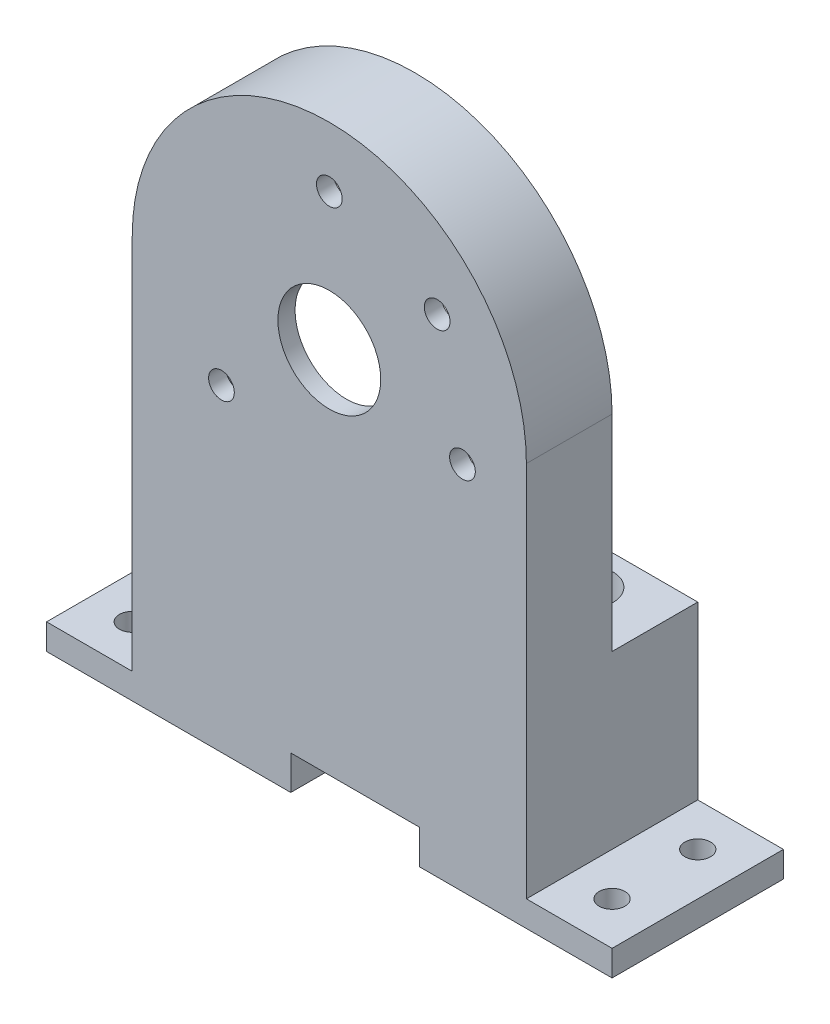
SolidWorks part; units mm, degrees
ref_plane "前视基准面" through (0, 0, 0) normal (0, 0, 1) x (1, 0, 0)
ref_plane "上视基准面" through (0, 0, 0) normal (0, 1, 0) x (1, 0, 0)
ref_plane "右视基准面" through (0, 0, 0) normal (1, 0, 0) x (0, 0, -1)
other "Configuration Table"
sketch "草图1" plane through (0, 0, 0) normal (0, 0, 1) x (1, 0, 0)
  line L0 (-23, 0) -> (-23, -27)
  line L1 (-23, -27) -> (23, -27)
  line L2 (23, -27) -> (23, 0)
  arc A1 (23, 0) -> (-23, 0) centre (0, 0) ccw
  dimension "D1" = 27
  dimension "D2" = 23
extrude "凸台-拉伸1" add sketch "草图1" along normal blind 20
sketch "草图2" plane through (0, 0, 0) normal (0, 0, -1) x (-1, 0, 0)
  line L0 (-23, -24) -> (23, -24)
  line L1 (23, 0) -> (23, -27) construction
  line L2 (-23, -27) -> (-23, 0) construction
  line L3 (-23, 0) -> (-23, -27)
  line L4 (-23, -27) -> (23, -27)
  line L5 (23, -27) -> (23, 0)
  line L6 (-23, 0) -> (-23, -24)
  line L8 (23, -24) -> (23, 0)
  arc A1 (23, 0) -> (-23, 0) centre (0, 0) ccw
  arc A2 (23, 0) -> (-23, 0) centre (0, 0) ccw
  dimension "D2" = 24
  dimension "D1" = 0
extrude "切除-拉伸1" cut sketch "草图2" against normal blind 10
sketch "草图3" plane through (0, 0, 10) normal (0, 0, -1) x (-1, 0, 0)
  circle A0 centre (0, 0) radius 21
extrude "切除-拉伸2" cut sketch "草图3" against normal blind 8
sketch "草图7" plane through (0, 0, 20) normal (0, 0, 1) x (1, 0, 0)
  circle A0 centre (0, 16) radius 1.5 construction
  circle A1 centre (0, 16) radius 1.5
  circle A2 centre (12.5891, 9.875) radius 1.5 construction
  circle A3 centre (12.5891, 9.875) radius 1.5
  circle A4 centre (-12.5891, -9.875) radius 1.5 construction
  circle A5 centre (15.5396, -3.8105) radius 1.5 construction
  circle A6 centre (-12.5891, -9.875) radius 1.5
  circle A7 centre (15.5396, -3.8105) radius 1.5
extrude "切除-拉伸6" cut sketch "草图7" against normal blind 3
sketch "草图8" plane through (0, 0, 18) normal (0, 0, -1) x (-1, 0, 0)
  circle A1 centre (0, 0) radius 6
  circle A2 centre (0, 0) radius 6
  dimension "D1" = 0
extrude "切除-拉伸7" cut sketch "草图8" against normal blind 3
sketch "草图12" plane through (0, -27, 0) normal (0, -1, 0) x (1, 0, 0)
  line L4 (-23, 0) -> (23, 0)
  line L5 (23, 0) -> (23, 20)
  line L6 (23, 20) -> (-23, 20)
  line L7 (-23, 20) -> (-23, 0)
  line L8 (-23, 0) -> (23, 0)
  line L9 (23, 0) -> (23, 20)
  line L10 (23, 20) -> (-23, 20)
  line L11 (-23, 20) -> (-23, 0)
  dimension "D1" = 0
extrude "凸台-拉伸4" add sketch "草图12" along normal blind 20
sketch "草图13" plane through (0, -24, 0) normal (0, 1, 0) x (1, 0, 0)
  line L0 (19.5, -5) -> (-24.0032, -5) construction
  line L1 (23, -10) -> (23, 0) construction
  line L2 (0, -11) -> (0, 11) construction
  circle A0 centre (15, -5) radius 3.1
  circle A1 centre (-15, -5) radius 3.1
  dimension "D1" = 8
extrude "切除-拉伸8" cut sketch "草图13" against normal blind 20
sketch "草图14" plane through (0, -47, 0) normal (0, -1, 0) x (1, 0, 0)
  line L0 (23, 20) -> (33, 20)
  line L1 (-33, 20) -> (-23, 20)
  line L2 (-33, 20) -> (-33, 0)
  line L3 (-33, 0) -> (-23, 0)
  line L4 (33, 20) -> (33, 0)
  line L6 (-23, 20) -> (-23, 0)
  line L8 (23, 20) -> (23, 0)
  line L9 (23, 0) -> (33, 0)
  circle A0 centre (28, 5) radius 1.5
  circle A1 centre (28, 15) radius 1.5
  circle A2 centre (-28, 5) radius 1.5
  circle A3 centre (-28, 15) radius 1.5
extrude "凸台-拉伸5" add sketch "草图14" against normal blind 3
sketch "草图15" plane through (0, -44, 0) normal (0, 1, 0) x (1, 0, 0)
  circle A0 centre (-15, -5) radius 1.5
  circle A1 centre (15, -5) radius 1.5
extrude "切除-拉伸9" cut sketch "草图15" against normal through all
sketch "草图16" plane through (0, -47, 0) normal (0, -1, 0) x (1, 0, 0)
  line L6 (-33, 0) -> (33, 0) construction
  line L8 (-4.5, 0) -> (-4.5, 20)
  line L9 (-4.5, 20) -> (10.5, 20)
  line L10 (10.5, 0) -> (10.5, 20)
  line L13 (33, 20) -> (-33, 20) construction
  line L14 (-4.5, 0) -> (10.5, 0)
  point P0 (0, 0)
  dimension "D1" = 15
extrude "切除-拉伸10" cut sketch "草图16" against normal blind 4
